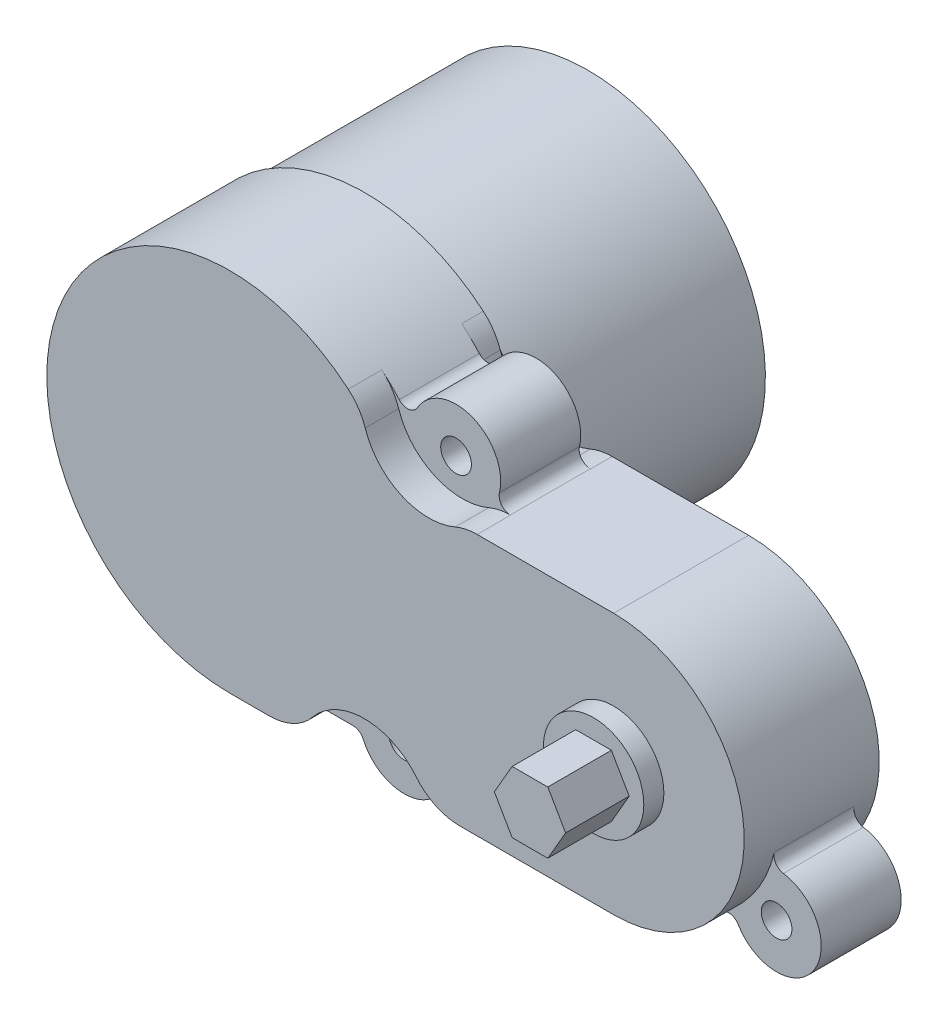
SolidWorks part; units mm, degrees
ref_plane "Front Plane" through (0, 0, 0) normal (0, 0, 1) x (1, 0, 0)
ref_plane "Top Plane" through (0, 0, 0) normal (0, 1, 0) x (1, 0, 0)
ref_plane "Right Plane" through (0, 0, 0) normal (1, 0, 0) x (0, 0, -1)
sketch "Sketch1" plane through (0, 0, 0) normal (0, 0, 1) x (1, 0, 0)
  line L0 (0, -16.4) -> (34.4, -16.4)
  line L1 (34.4, 7) -> (14.831, 7)
  arc A0 (14.831, 7) -> (0, -16.4) centre (0, 0) ccw
  arc A1 (34.4, -16.4) -> (34.4, 7) centre (34.4, -4.7) ccw
  dimension "D1" = 32.8
  dimension "D2" = 23.4
  dimension "D3" = 62.5
extrude "Boss-Extrude1" add sketch "Sketch1" along normal blind 12.1
ref_plane "Plane1" through (0, 0, 9.1) normal (0, 0, 1) x (1, 0, 0)
sketch "Sketch2" plane through (0, 0, 9.1) normal (0, 0, 1) x (1, 0, 0)
  line L0 (0, -16.4) -> (34.4, -16.4) construction
  line L1 (12.6224, -15.4) -> (68.6762, -15.4) construction
  circle A0 centre (17.2763, 9.163) radius 4
  circle A1 centre (46, -12.5384) radius 4
  circle A2 centre (12.6224, -15.4) radius 4
  arc A3 (34.4, -16.4) -> (34.4, 7) centre (34.4, -4.7) ccw construction
  arc A4 (14.831, 7) -> (0, -16.4) centre (0, 0) ccw construction
  dimension "D1" = 8
  dimension "D5" = 14
  dimension "D6" = 3
  dimension "D7" = 66.4
  dimension "D2" = 25
  dimension "D3" = 33.5
  dimension "D4" = 36
  dimension "D8" = 2.8616
extrude "Boss-Extrude2" add sketch "Sketch2" against normal blind 7.17
sketch "Sketch3" plane through (0, 0, 0) normal (0, 0, -1) x (-1, 0, 0)
  circle A0 centre (0, 0) radius 15.9
  dimension "D1" = 31.8
extrude "Boss-Extrude3" add sketch "Sketch3" along normal blind 20
sketch "Sketch4" plane through (0, 0, -20) normal (0, 0, -1) x (-1, 0, 0)
  circle A0 centre (0, 0) radius 3.75
  dimension "D1" = 7.5
extrude "Boss-Extrude4" add sketch "Sketch4" along normal blind 3.2
sketch "Sketch5" plane through (0, 0, 12.1) normal (0, 0, 1) x (1, 0, 0)
  circle A0 centre (34.4, -4.7) radius 4.5
  dimension "D1" = 9
extrude "Boss-Extrude5" add sketch "Sketch5" along normal blind 1.8
sketch "Sketch6" plane through (0, 0, 13.9) normal (0, 0, 1) x (1, 0, 0)
  line L1 (35.9964, -7.465) -> (37.5927, -4.7)
  line L2 (37.5927, -4.7) -> (35.9964, -1.935)
  line L3 (35.9964, -1.935) -> (32.8036, -1.935)
  line L4 (32.8036, -1.935) -> (31.2073, -4.7)
  line L5 (31.2073, -4.7) -> (32.8036, -7.465)
  line L6 (32.8036, -7.465) -> (35.9964, -7.465)
  circle A0 centre (34.4, -4.7) radius 2.765 construction
  dimension "D1" = 5.53
extrude "Boss-Extrude6" add sketch "Sketch6" along normal offset from surface (5.7 mm away) 7.5 up to face at (38.9, -4.7, 12.1) offset beyond the face yes
sketch "Sketch8" plane through (0, 0, 12.1) normal (0, 0, 1) x (1, 0, 0)
  line L0 (17.2763, 9.163) -> (16.7178, 6.2154) construction
  line L1 (17.2763, 9.163) -> (17.8348, 12.1106) construction
  line L2 (12.6224, -15.4) -> (13.1809, -12.4524) construction
  line L3 (12.064, -18.3476) -> (12.6224, -15.4) construction
  circle A0 centre (17.8348, 12.1106) radius 6
  circle A1 centre (12.064, -18.3476) radius 6
  point P6 (17.2763, 9.163)
  point P7 (17.8348, 12.1106)
  point P8 (12.6224, -15.4)
  dimension "D1" = 3
  dimension "D2" = 12
extrude "Cut-Extrude2" cut sketch "Sketch8" against normal up to surface (3 mm away) up to face at (16.8236, 9.4224, 9.1)
sketch "Sketch7" plane through (0, 0, 9.1) normal (0, 0, 1) x (1, 0, 0)
  circle A0 centre (17.2763, 9.163) radius 1.375
  circle A1 centre (46, -12.5384) radius 1.375
  circle A2 centre (12.6224, -15.4) radius 1.375
  dimension "D1" = 2.75
extrude "Cut-Extrude1" cut sketch "Sketch7" against normal through all
sketch "Sketch9" plane through (0, 0, 0) normal (0, 0, -1) x (-1, 0, 0)
  circle A0 centre (-12.064, -18.3476) radius 6 construction
  circle A1 centre (-17.8348, 12.1106) radius 6 construction
  circle A2 centre (-12.064, -18.3476) radius 6
  circle A3 centre (-17.8348, 12.1106) radius 6
extrude "Cut-Extrude3" cut sketch "Sketch9" against normal up to surface (1.93 mm away) up to face at (18.6513, 9.163, 1.93)
fillet "Fillet1" radius 1 6 edges at (8.7495, -16.4, 5.515) (16.4954, -16.4, 5.515) (42.1161, -13.495, 5.515) (45.4386, -8.578, 5.515) (13.2998, 9.5956, 5.515) (20.641, 7, 5.515)
fillet "Fillet2" radius 5 8 edges at (6.3889, -16.4, 0.965) (17.7391, -16.4, 0.965) (6.3889, -16.4, 10.6) (17.7391, -16.4, 10.6) (11.8905, 11.295, 0.965) (21.4232, 7.3019, 0.965) (21.4232, 7.3019, 10.6) (11.8905, 11.295, 10.6)
ref_plane "Plane for mirroring part" through (-23, 0, 0) normal (1, 0, 0) x (0, 0, -1)
